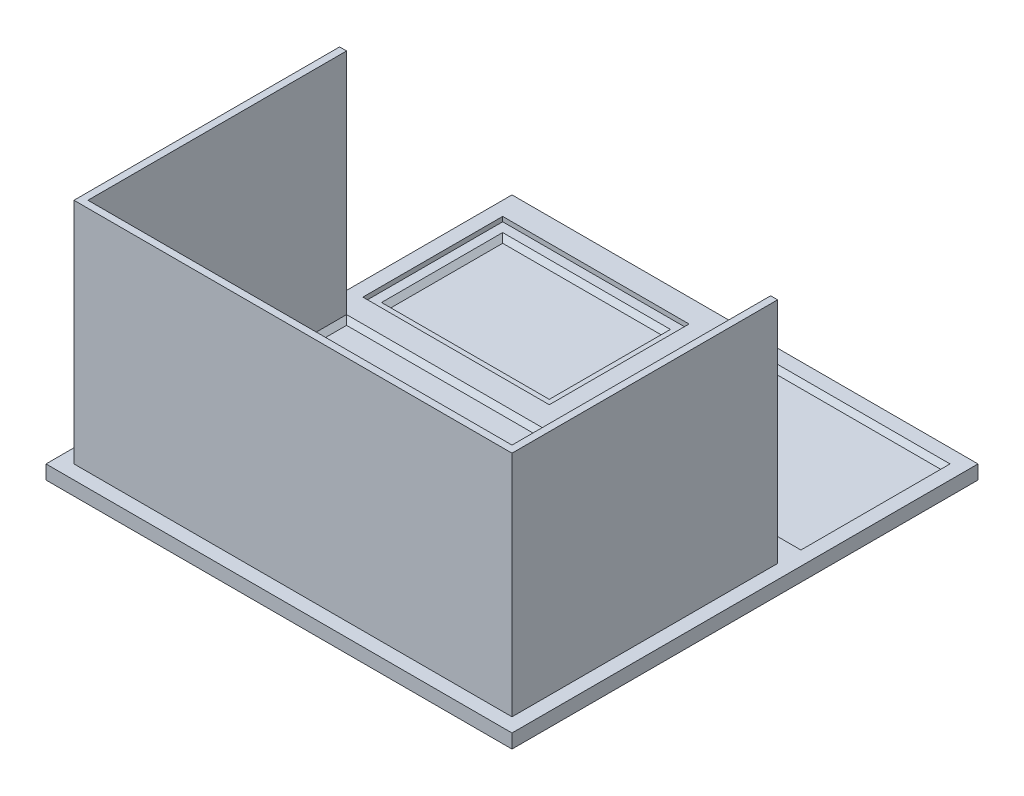
SolidWorks part; units mm, degrees
ref_plane "Front Plane" through (0, 0, 0) normal (0, 0, 1) x (1, 0, 0)
ref_plane "Top Plane" through (0, 0, 0) normal (0, 1, 0) x (1, 0, 0)
ref_plane "Right Plane" through (0, 0, 0) normal (1, 0, 0) x (0, 0, -1)
sketch "Sketch1" plane through (0, 0, 0) normal (0, 1, 0) x (1, 0, 0)
  line L1 (0, 0) -> (1000, 0)
  line L2 (0, 0) -> (0, -1000)
  line L3 (0, -1000) -> (1000, -1000)
  line L4 (1000, 0) -> (1000, -1000)
  dimension "D1" = 1000
  dimension "D2" = 1000
extrude "Boss-Extrude1" add sketch "Sketch1" along normal blind 30
sketch "Sketch2" plane through (0, 30, 0) normal (0, 1, 0) x (1, 0, 0)
  line L0 (1000, 0) -> (0, 0) construction
  line L1 (30, -50) -> (430, -50)
  line L2 (30, -50) -> (30, -350)
  line L3 (30, -350) -> (430, -350)
  line L4 (430, -50) -> (430, -350)
  line L5 (0, 0) -> (0, -1000) construction
  dimension "D1" = 300
  dimension "D2" = 400
  dimension "D3" = 50
  dimension "D4" = 30
extrude "Cut-Extrude1" cut sketch "Sketch2" against normal blind 20
sketch "Sketch3" plane through (0, 10, 0) normal (0, 1, 0) x (1, 0, 0)
  line L1 (30, -50) -> (430, -50)
  line L2 (30, -50) -> (30, -350)
  line L3 (30, -350) -> (430, -350)
  line L4 (430, -50) -> (430, -350)
  line L5 (50, -70) -> (410, -70)
  line L6 (50, -70) -> (50, -330)
  line L7 (50, -330) -> (410, -330)
  line L8 (410, -70) -> (410, -330)
  dimension "D1" = 20
  dimension "D2" = 20
  dimension "D3" = 20
  dimension "D4" = 20
extrude "Boss-Extrude2" add sketch "Sketch3" along normal blind 10
chamfer "Chamfer1" distance 10 angle 45 4 edges at (230, 10, 70) (410, 10, 200) (230, 10, 330) (50, 10, 200)
sketch "Sketch5" plane through (0, 30, 0) normal (0, 1, 0) x (1, 0, 0)
  line L0 (0, 0) -> (0, -1000) construction
  line L1 (0, -1000) -> (1000, -1000) construction
  line L2 (1000, -1000) -> (1000, 0) construction
  line L4 (1000, 0) -> (0, 0) construction
  line L6 (430, -350) -> (430, -50) construction
  line L7 (480, -30) -> (970, -30)
  line L8 (480, -30) -> (480, -350)
  line L9 (480, -350) -> (970, -350)
  line L10 (970, -30) -> (970, -350)
  line L11 (30, -400) -> (970, -400)
  line L12 (30, -400) -> (30, -970)
  line L13 (30, -970) -> (970, -970)
  line L14 (970, -400) -> (970, -970)
  line L15 (30, -350) -> (430, -350) construction
  dimension "D1" = 30
  dimension "D2" = 30
  dimension "D3" = 30
  dimension "D4" = 30
  dimension "D5" = 30
  dimension "D6" = 50
  dimension "D7" = 50
  dimension "D8" = 50
extrude "Cut-Extrude2" cut sketch "Sketch5" against normal blind 10
sketch "Sketch7" plane through (0, 20, 0) normal (0, 1, 0) x (1, 0, 0)
  line L0 (970, -400) -> (955, -400)
  line L1 (970, -400) -> (30, -400) construction
  line L2 (955, -400) -> (955, -955)
  line L3 (955, -955) -> (45, -955)
  line L4 (45, -955) -> (45, -400)
  line L5 (970, -400) -> (30, -400) construction
  line L6 (45, -400) -> (30, -400)
  line L7 (30, -400) -> (30, -970)
  line L8 (30, -970) -> (970, -970)
  line L9 (970, -970) -> (970, -400)
  dimension "D1" = 15
  dimension "D2" = 15
  dimension "D3" = 15
extrude "Boss-Extrude5" add sketch "Sketch7" along normal blind 500
chamfer "Chamfer3" distance 10 angle 45 8 edges at (725, 20, 30) (970, 20, 190) (725, 20, 350) (480, 20, 190) (45, 20, 677.5) (500, 20, 400) (955, 20, 677.5) (500, 20, 955)
